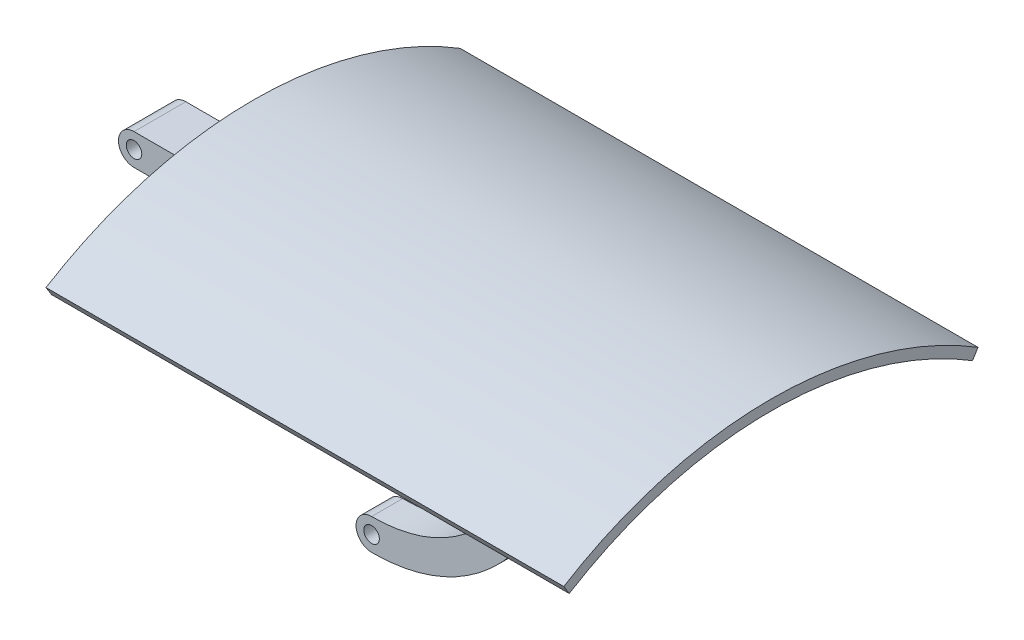
SolidWorks part; units mm, degrees
ref_plane "Plan de face" through (0, 0, 0) normal (0, 0, 1) x (1, 0, 0)
ref_plane "Plan de dessus" through (0, 0, 0) normal (0, 1, 0) x (1, 0, 0)
ref_plane "Plan de droite" through (0, 0, 0) normal (1, 0, 0) x (0, 0, -1)
sketch "Esquisse1" plane through (0, 0, 0) normal (1, 0, 0) x (0, 0, -1)
  line L0 (-40, 64.8571) -> (0, 0) construction
  line L1 (0, 0) -> (40, 64.8571) construction
  line L2 (-40, 64.8571) -> (40, 64.8571) construction
  line L3 (0, 64.8571) -> (0, 0) construction
  line L4 (-40, 64.8571) -> (-38.9501, 63.1548)
  line L5 (40, 64.8571) -> (38.9501, 63.1548)
  arc A0 (-40, 64.8571) -> (40, 64.8571) centre (0, 0) cw
  arc A1 (-38.9501, 63.1548) -> (38.9501, 63.1548) centre (0, 0) cw
  dimension "D1" = 76.2
  dimension "D2" = 63.328
  dimension "D3" = 2
  dimension "D4" = 80
extrude "Boss.-Extru.1" add sketch "Esquisse1" along normal blind 100
sketch "Esquisse3" plane through (0, 0, 0) normal (0, 0, 1) x (1, 0, 0)
  line L0 (60, 74.2) -> (60, 69.2)
  line L1 (100, 74.2) -> (0, 74.2) construction
  line L2 (60, 69.2) -> (66, 69.2) construction
  line L3 (66, 69.2) -> (66, 74.2)
  line L4 (66, 74.2) -> (60, 74.2)
  line L5 (0, 76.2) -> (0, 64.8571) construction
  line L6 (60, 49.3364) -> (60, 89.1606) construction
  line L7 (25.8781, 21) -> (25.8781, 15) construction
  line L8 (8.5798, 21) -> (42.5207, 21) construction
  line L9 (2.0573, 15) -> (44.8483, 15) construction
  line L10 (60, 69.2) -> (66, 69.2) construction
  line L11 (7.2581, 15) -> (51.6413, 15) construction
  arc A0 (25.8781, 21) -> (25.8781, 15) centre (25.8781, 18) ccw
  circle A1 centre (25.8781, 18) radius 1.5
  spline S0 degree 3 poles (60, 69.2) (60, 40.51) (46.6386, 21) (25.8781, 21) knots 0 0 0 0 1 1 1 1
  spline S1 degree 3 poles (66, 69.2) (66, 41.462) (51.7533, 15) (25.8781, 15) knots 0 0 0 0 1 1 1 1
  dimension "D4" = 3
  dimension "D1" = 60
  dimension "D2" = 5
  dimension "D3" = 6
  dimension "D5" = 56.2
extrude "Boss.-Extru.2" add sketch "Esquisse3" along normal blind 3 and the other way blind 3 contours L3 L4 L0 S0 A0 S1 | A1
sketch "Esquisse7" plane through (0, 0, 0) normal (0, 0, 1) x (1, 0, 0)
  line L0 (7, 74.2) -> (7, 73.5443)
  line L1 (60, 74.2) -> (0, 74.2) construction
  line L2 (7, 74.2) -> (13, 74.2)
  line L3 (13, 74.2) -> (13, 70.4183)
  line L4 (13, 70.4183) -> (-4.539, 58.4394)
  line L5 (-4.539, 58.4394) -> (-18, 58.4394)
  line L6 (-18, 58.4394) -> (-18, 64.4394) construction
  line L7 (-18, 64.4394) -> (-6.3311, 64.4394)
  line L8 (-6.3311, 64.4394) -> (7, 73.5443)
  line L9 (4.2305, 64.4288) -> (0.3345, 68.9918) construction
  line L10 (10, 74.2) -> (0, 74.2) construction
  line L11 (-18, 61.4394) -> (-6.3311, 61.4394) construction
  line L12 (-6.3311, 61.4394) -> (-6.3311, 64.4394) construction
  line L13 (-6.3311, 61.4394) -> (-6.3311, 58.4394) construction
  circle A0 centre (-18, 61.4394) radius 1.5
  arc A1 (-18, 64.4394) -> (-18, 58.4394) centre (-18, 61.4394) ccw
  dimension "D3" = 3
  dimension "D1" = 6
  dimension "D2" = 10
  dimension "D4" = 28
  dimension "D5" = 12.7606
extrude "Boss.-Extru.3" add sketch "Esquisse7" along normal blind 5 and the other way blind 5 contours L7 L8 L0 L2 L3 L4 L5 A1 | A0
ref_plane "Plan2" through (0, 61.4394, 0) normal (0, 1, 0) x (1, 0, 0)
